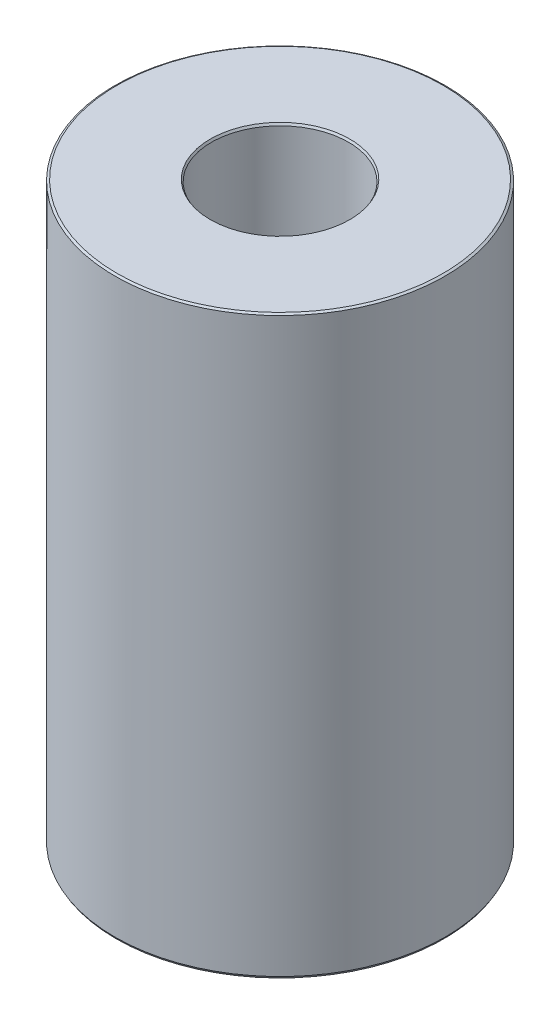
SolidWorks part; units mm, degrees
ref_plane "Front Plane" through (0, 0, 0) normal (0, 0, 1) x (1, 0, 0)
ref_plane "Top Plane" through (0, 0, 0) normal (0, 1, 0) x (1, 0, 0)
ref_plane "Right Plane" through (0, 0, 0) normal (1, 0, 0) x (0, 0, -1)
sketch "Sketch1" plane through (0, 0, 0) normal (0, 1, 0) x (1, 0, 0)
  circle A0 centre (0, 0) radius 35
  dimension "SLEEVE_OD" = 70
extrude "Boss-Extrude1" add sketch "Sketch1" along normal blind 122.0433
sketch "Sketch2" plane through (0, 0, 0) normal (0, 1, 0) x (1, 0, 0)
  circle A0 centre (0, 0) radius 14.5372
  dimension "BORE_D" = 29.0743
extrude "Cut-Extrude1" cut sketch "Sketch2" along normal through all
chamfer "Chamfer1" distance 0.2625 angle 60 4 edges at (0, 122.0433, 14.5372) (0, 0, 14.5372) (0, 0, 35) (0, 122.0433, 35) first distance on face at (0, 122.0433, 14.5372) first distance on face at (0, 0, 14.5372) first distance on face at (0, 122.0433, 35)
